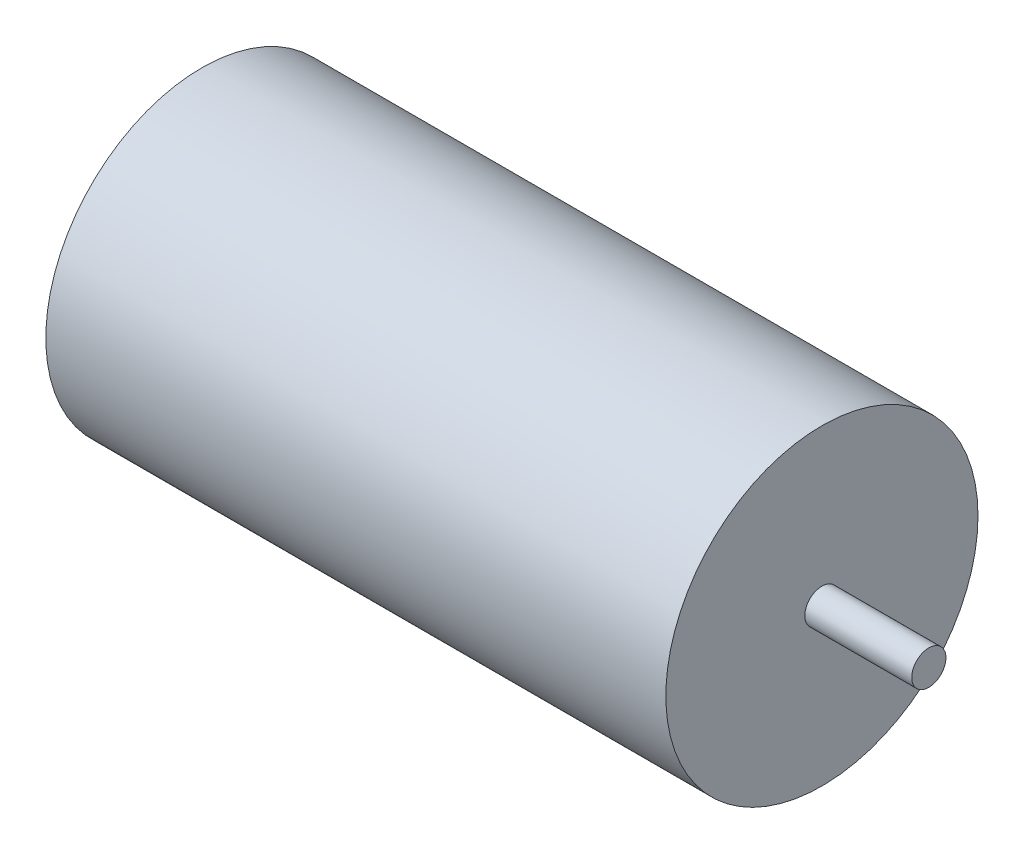
SolidWorks part; units mm, degrees
ref_plane "Front Plane" through (0, 0, 0) normal (0, 0, 1) x (1, 0, 0)
ref_plane "Top Plane" through (0, 0, 0) normal (0, 1, 0) x (1, 0, 0)
ref_plane "Right Plane" through (0, 0, 0) normal (1, 0, 0) x (0, 0, -1)
sketch "Sketch1" plane through (0, 0, 0) normal (1, 0, 0) x (0, 0, -1)
  circle A0 centre (0, 0) radius 4
  circle A1 centre (0, 0) radius 36.5
  dimension "D1" = 73
  dimension "D2" = 8
extrude "Boss-Extrude1" add sketch "Sketch1" along normal blind 145 contours A1 A0 region at (0, 0, 35.4676)
extrude "Boss-Extrude2" add sketch "Sketch1<3>" along normal blind 170 and the other way blind 22 contours A0 region at (0, 0, 0)
sketch "Sketch1<3>" plane through (0, 0, 0) normal (1, 0, 0) x (0, 0, -1) same geometry as "Sketch1"
